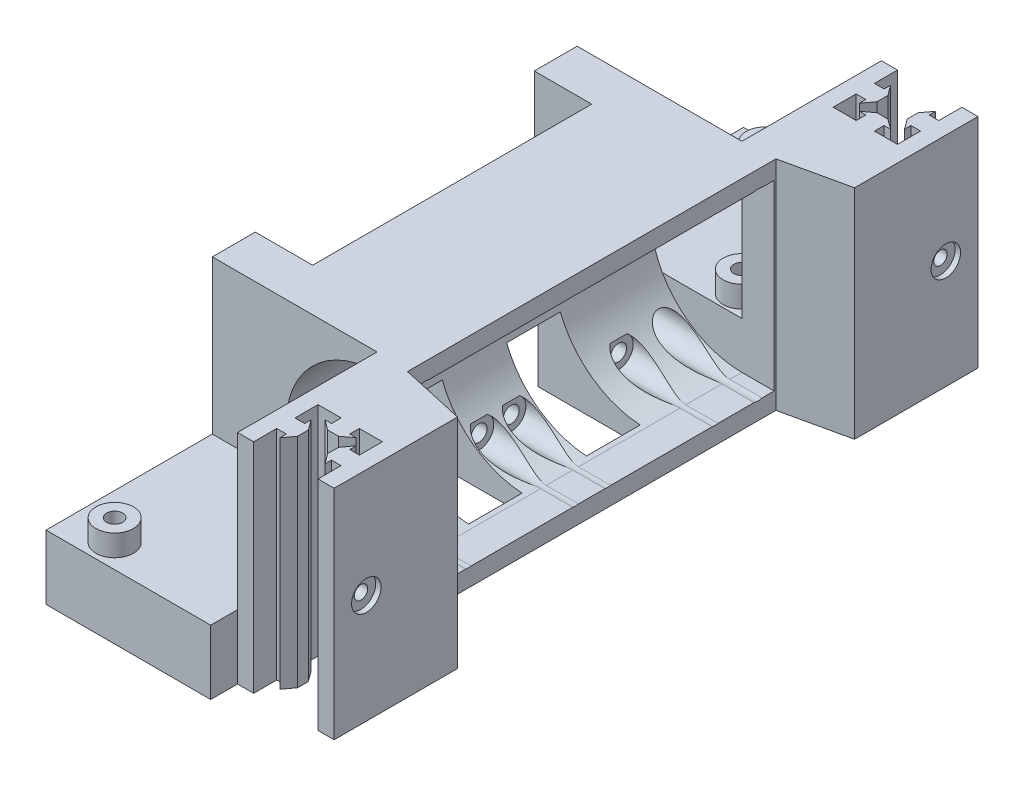
SolidWorks part; units mm, degrees
ref_plane "Plan de face" through (0, 0, 0) normal (0, 0, 1) x (1, 0, 0)
ref_plane "Plan de dessus" through (0, 0, 0) normal (0, 1, 0) x (1, 0, 0)
ref_plane "Plan de droite" through (0, 0, 0) normal (1, 0, 0) x (0, 0, -1)
ref_plane "Plan milieu" through (0, 0, -54) normal (0, 0, 1) x (1, 0, 0)
ref_axis "Axe1" through (0, 19.3307, 0) along (0, -1, 0)
ref_axis "Axe2" through (23.7847, 0, 0) along (-1, 0, 0)
ref_axis "Axe3" through (0, 0, -92.2336) along (0, 0, 1)
sketch "Esquisse8" plane through (0, 0, 0) normal (0, 1, 0) x (1, 0, 0)
  line L0 (-6, 1.7) -> (-4.2, 1.7)
  line L1 (0, -17.9979) -> (0, 17.9979) construction
  line L2 (-4.2, 1.7) -> (-4.2, 2.9)
  line L3 (-4.2, 2.9) -> (-2.8, 1)
  line L4 (-2.8, 1) -> (-2.8, -1)
  line L5 (-2.8, -1) -> (-4.2, -2.9)
  line L6 (-4.2, -2.9) -> (-4.2, -1.7)
  line L7 (-4.2, -1.7) -> (-6, -1.7)
  line L8 (-6, -1.7) -> (-6, -9)
  line L9 (-6, -9) -> (-9, -9)
  line L10 (-9, -9) -> (-9, 9)
  line L11 (-9, 9) -> (-6, 9)
  line L12 (-6, 9) -> (-6, 1.7)
  line L16 (23.7847, 0) -> (-17.9556, 0) construction
  point P14 (-2.8, 0)
  dimension "D1" = 1.8
  dimension "D2" = 3.2
  dimension "D3" = 18
  dimension "D4" = 2
  dimension "D5" = 1.2
  dimension "D7" = 3
  dimension "D8" = 3.4
  dimension "D9" = 6
extrude "Boss.-Extru.6" add sketch "Esquisse8" along normal mid plane 40.6 separate body
pattern_circular "Répétition circulaire3" count 3 every 90 about axis through (0, 19.3307, 0) along (0, -1, 0) of bodies 117
sketch "Esquisse9" plane through (0, 20.3, 0) normal (0, 1, 0) x (1, 0, 0)
  line L0 (9, -9) -> (9, 9) construction
  line L1 (-9, -9) -> (9, -9)
  line L2 (-9, -9) -> (-9, -6)
  line L3 (-9, -6) -> (9, -6)
  line L4 (9, -9) -> (9, -6)
  dimension "D1" = 3
extrude "Enlèv. mat.-Extru.1" cut sketch "Esquisse9" against normal through all
sketch "Esquisse10" plane through (0, 0, -9) normal (0, 0, -1) x (-1, 0, 0)
  line L0 (6, -20.3) -> (9, -20.3) construction
  line L1 (9, 20.3) -> (3, 20.3)
  line L2 (9, 20.3) -> (9, -20.3)
  line L3 (9, -20.3) -> (3, -20.3)
  line L4 (3, 20.3) -> (3, -20.3)
  line L5 (-9, -20.3) -> (9, -20.3) construction
  dimension "D1" = 6
extrude "Boss.-Extru.7" add sketch "Esquisse10" along normal up to surface (45 mm away) up to plane "Plan milieu"
sketch "Esquisse13" plane through (0, -20.3, 0) normal (0, -1, 0) x (-1, 0, 0)
  line L0 (9, 21) -> (-9, 17)
  line L1 (9, 54) -> (9, -6) construction
  line L2 (9, 21) -> (9, 9)
  line L3 (9, 9) -> (-9, 9)
  line L4 (-9, 6) -> (-9, 9) construction
  line L5 (-9, 17) -> (-9, 9)
  line L6 (9, 54) -> (9, -6) construction
  dimension "D1" = 12
  dimension "D2" = 8
extrude "Boss.-Extru.8" add sketch "Esquisse13" against normal up to surface (40.6 mm away) up to face at (-1.9333, 20.3, -7.6208)
sketch "Esquisse15" plane through (9, 0, 0) normal (1, 0, 0) x (0, 0, -1)
  line L0 (-6, -20.3) -> (-6, 20.3) construction
  line L2 (0, 19.3307) -> (0, -16.6651) construction
  circle A0 centre (0, 0) radius 1.25
  point P2 (-6, 0)
  dimension "D1" = 2.5
extrude "Enlèv. mat.-Extru.3" cut sketch "Esquisse15" against normal up to next
sketch "Esquisse19" plane through (9, 0, 0) normal (1, 0, 0) x (0, 0, -1)
  circle A0 centre (0, 0) radius 2.75
  circle A1 centre (0, 0) radius 1.25 construction
  dimension "D1" = 5.5
extrude "Enlèv. mat.-Extru.5" cut sketch "Esquisse19" against normal blind 1
sketch "Esquisse20" plane through (-9, 0, 0) normal (-1, 0, 0) x (0, 0, 1)
  line L0 (6, -20.3) -> (-54, -20.3) construction
  line L1 (-20, -20.3) -> (11, -20.3)
  line L2 (-20, -20.3) -> (-20, -8.3)
  line L3 (-20, -8.3) -> (11, -8.3)
  line L4 (11, -20.3) -> (11, -8.3)
  line L5 (6, -20.3) -> (6, 20.3) construction
  dimension "D1" = 31
  dimension "D2" = 12
  dimension "D3" = 5
extrude "Boss.-Extru.9" add sketch "Esquisse20" along normal blind 30.7
sketch "Esquisse21" plane through (0, -8.3, 0) normal (0, 1, 0) x (1, 0, 0)
  line L0 (-39.7, -11) -> (-39.7, 20) construction
  line L1 (-39.7, -11) -> (-9, -11) construction
  line L2 (-9, -6) -> (-9, 20) construction
  line L3 (-39.7, 20) -> (-9, 20) construction
  circle A0 centre (-31.3, -6.6) radius 3.5
  circle A1 centre (-13, 16) radius 3.5
  dimension "D1" = 7
  dimension "D4" = 4
  dimension "D2" = 8.4
  dimension "D3" = 4.4
  dimension "D5" = 4
extrude "Boss.-Extru.10" add sketch "Esquisse21" along normal blind 4
sketch "Esquisse22" plane through (0, -4.3, 0) normal (0, 1, 0) x (1, 0, 0)
  circle A0 centre (-13, 16) radius 1.5
  circle A1 centre (-13, 16) radius 3.5 construction
  circle A2 centre (-31.3, -6.6) radius 1.5
  dimension "D1" = 3
extrude "Enlèv. mat.-Extru.6" cut sketch "Esquisse22" against normal through all
sketch "Esquisse23" plane through (0, 0, -20) normal (0, 0, -1) x (-1, 0, 0)
  line L0 (39.7, -20.3) -> (9, -20.3) construction
  line L1 (29, -20.3) -> (5, -20.3)
  line L2 (29, -20.3) -> (29, 20.3)
  line L3 (29, 20.3) -> (5, 20.3)
  line L4 (5, -20.3) -> (5, 20.3)
  line L5 (9, -20.3) -> (9, 20.3) construction
  line L6 (9, 20.3) -> (3, 20.3) construction
  dimension "D1" = 24
  dimension "D2" = 4
extrude "Boss.-Extru.11" add sketch "Esquisse23" along normal blind 34
ref_plane "Plan1" through (9, 0, 0) normal (1, 0, 0) x (0, 0, -1)
ref_plane "Plan2" through (-9, 0, 0) normal (-1, 0, 0) x (0, 0, 1)
ref_plane "Plan3" through (-21, 0, 0) normal (-1, 0, 0) x (0, 0, 1)
sketch "Esquisse24" plane through (0, 0, -54) normal (0, 0, 1) x (1, 0, 0)
  line L0 (15.0486, 0) -> (-15.0486, 0) construction
  line L1 (-9, 17) -> (11, 17)
  line L2 (11, 17) -> (11, -17)
  line L3 (11, -17) -> (-9, -17)
  line L4 (-9, 24.9234) -> (-9, -24.9234) construction
  arc A1 (-9, 17) -> (-9, -17) centre (-9, 0) ccw
  dimension "D2" = 17
  dimension "D3" = 20
extrude "Enlèv. mat.-Extru.7" cut sketch "Esquisse24" along normal up to surface (34 mm away) up to face at (-19, 6, -20)
sketch "Esquisse25" plane through (-29, 0, 0) normal (-1, 0, 0) x (0, 0, 1)
  line L0 (-54, 20.3) -> (-20, 20.3) construction
  line L1 (-28, -20.3) -> (-20, -20.3)
  line L2 (-28, -20.3) -> (-28, 20.3)
  line L3 (-28, 20.3) -> (-20, 20.3)
  line L4 (-20, -20.3) -> (-20, 20.3)
  line L5 (-54, -20.3) -> (-20, -20.3) construction
  line L6 (-20, -8.3) -> (-20, 20.3) construction
  dimension "D1" = 8
extrude "Boss.-Extru.16" add sketch "Esquisse25" along normal up to surface (10.7 mm away) up to face at (-39.7, -14.3, -4.5)
sketch "Esquisse26" plane through (-29, 0, 0) normal (-1, 0, 0) x (0, 0, 1)
  line L0 (-54, 20.3) -> (-28, 20.3) construction
  line L1 (-28, 20.3) -> (-28, -20.3) construction
  circle A0 centre (-31, 14.3) radius 1.5
  dimension "D1" = 3
  dimension "D2" = 6
  dimension "D3" = 3
extrude "Enlèv. mat.-Extru.8" cut sketch "Esquisse26" against normal through all
sketch "Esquisse29" plane through (-21, 0, 0) normal (-1, 0, 0) x (0, 0, 1)
  circle A0 centre (-31, 14.3) radius 2.75
  circle A1 centre (-31, 14.3) radius 1.5 construction
  dimension "D1" = 5.5
extrude "Enlèv. mat.-Extru.13" cut sketch "Esquisse29" against normal through all
pattern_linear "Répétition linéaire1" count 2 spacing 20 along (0, 0, -1) of "Enlèv. mat.-Extru.8", "Enlèv. mat.-Extru.13"
mirror "Symétrie2" about plane through (0, 0, 0) normal (0, 1, 0) of "Répétition linéaire1"
sketch "Esquisse28" plane through (-29, 0, 0) normal (-1, 0, 0) x (0, 0, 1)
  line L0 (-28, 20.3) -> (-28, -20.3) construction
  line L1 (-28, 10) -> (-54, 10)
  line L2 (-28, 10) -> (-28, -10)
  line L3 (-28, -10) -> (-54, -10)
  line L4 (-54, 10) -> (-54, -10)
  line L5 (-54, -20.3) -> (-54, 20.3) construction
  line L6 (15.0486, 0) -> (-15.0486, 0) construction
  point P8 (-28, 0)
  dimension "D1" = 20
extrude "Boss.-Extru.17" add sketch "Esquisse28" along normal blind 4
sketch "Esquisse30" plane through (-33, 0, 0) normal (-1, 0, 0) x (0, 0, 1)
  line L0 (15.0486, 0) -> (-15.0486, 0) construction
  line L1 (-28, -20.3) -> (-28, 20.3) construction
  circle A0 centre (-31, 0) radius 1.5
  circle A1 centre (-31, 14.3) radius 1.5 construction
  dimension "D1" = 3
extrude "Enlèv. mat.-Extru.14" cut sketch "Esquisse30" against normal through all
pattern_linear "Répétition linéaire2" count 2 spacing 20 along (0, 0, -1) of "Enlèv. mat.-Extru.14"
sketch "Esquisse31" plane through (-29, 0, 0) normal (-1, 0, 0) x (0, 0, 1)
  circle A0 centre (-31, 0) radius 2.8
  dimension "D1" = 5.6
extrude "Enlèv. mat.-Extru.15" cut sketch "Esquisse31" against normal through all
ref_plane "Plan7" through (0, 0, -48) normal (0, 0, 1) x (1, 0, 0)
sketch "Esquisse34" plane through (0, 0, -48) normal (0, 0, 1) x (1, 0, 0)
  line L0 (-26.295, -5.3147) -> (-36.295, -22.6353)
  line L1 (-26.295, -5.3147) -> (-9, -15.3)
  line L2 (-13.235, -22.6353) -> (-9, -15.3)
  line L3 (-9, 24.9234) -> (-9, -24.9234) construction
  line L5 (-36.295, -22.6353) -> (-13.235, -22.6353)
  line L7 (-29, -20.3) -> (-3, -20.3) construction
  dimension "D1" = 20
  dimension "D2" = 60
  dimension "D4" = 5
extrude "Enlèv. mat.-Extru.20" cut sketch "Esquisse34" along normal blind 10
sketch "Esquisse35" plane through (-39.7, 0, 0) normal (-1, 0, 0) x (0, 0, 1)
  line L1 (-28, -20.3) -> (-28, 20.3) construction
  line L2 (-28, -20.3) -> (11, -20.3) construction
  circle A0 centre (-23, -14.3) radius 1.25
  dimension "D1" = 2.5
  dimension "D2" = 5
  dimension "D3" = 6
extrude "Enlèv. mat.-Extru.22" cut sketch "Esquisse35" against normal blind 20
sketch "Esquisse36" plane through (-29, 0, 0) normal (-1, 0, 0) x (0, 0, 1)
  circle A0 centre (-23, -14.3) radius 2.8
  circle A1 centre (-23, -14.3) radius 1.25 construction
  dimension "D1" = 5.6
extrude "Enlèv. mat.-Extru.23" cut sketch "Esquisse36" against normal through all
pattern_linear "Répétition linéaire4" count 3 spacing 12 along (0, 0, 1) of "Enlèv. mat.-Extru.22"
mirror "Symétrie9" about plane through (0, 0, 0) normal (0, 1, 0) of "Enlèv. mat.-Extru.22", "Enlèv. mat.-Extru.23"
mirror "Symétrie10" about plane through (0, 0, -54) normal (0, 0, 1) of bodies 176
